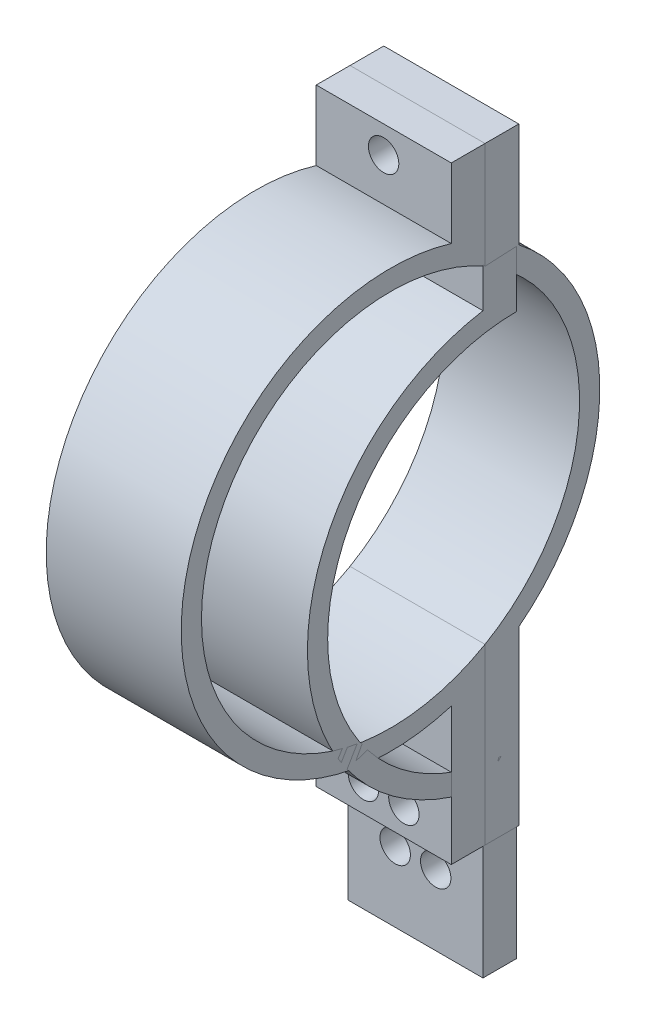
SolidWorks part; units mm, degrees
other "v1"
other "v2.1"
other "v2.2"
ref_plane "Front Plane" through (0, 0, 0) normal (1, 0, 0) x (0, 1, 0)
ref_plane "Top Plane" through (0, 0, 0) normal (0, 0, 1) x (0, 1, 0)
ref_plane "Right Plane" through (0, 0, 0) normal (0, 1, 0) x (-1, 0, 0)
sketch "Sketch1" plane through (0, 0, 0) normal (1, 0, 0) x (0, 1, 0)
  line L0 (0, 0) -> (-45, 0)
  line L1 (-45, -5) -> (45, -5)
  line L2 (-45, -5) -> (-45, 5)
  line L3 (-45, 5) -> (45, 5)
  line L4 (45, -5) -> (45, 5)
  line L5 (-45, -5) -> (45, 5) construction
  line L6 (-45, 5) -> (45, -5) construction
  line L7 (-45, 0) -> (0, 0)
  line L8 (0, 0) -> (45, 0)
  circle A0 centre (0, 0) radius 28
  circle A1 centre (0, 0) radius 31
  dimension "D1" = 56
  dimension "D2" = 62
  dimension "D3" = 10
  dimension "D4" = 90
extrude "Boss-Extrude1" add sketch "Sketch1" along normal blind 20 contours L3 A1 A0 | L3 A1 L7 A0 | A1 L3 L2 L0 | A1 L8 L4 L3 | L8 A1 L3 A0 region at (0, -29.3572, 2.5061) region at (0, 29.3572, 2.5061) region at (0, -37.932, 2.5119) region at (0, -29.072, 5.6648) region at (0, 37.932, 2.5119)
sketch "Sketch3" plane through (0, -45, 0) normal (0, -1, 0) x (1, 0, 0)
  line L4 (0, 5) -> (0, 0)
  line L5 (0, 0) -> (20, 0)
  line L6 (20, 0) -> (20, 5)
  line L7 (20, 5) -> (0, 5)
  line L8 (0, 5) -> (0, 0)
  line L9 (0, 0) -> (20, 0)
  line L10 (20, 0) -> (20, 5)
  line L11 (20, 5) -> (0, 5)
  dimension "D1" = 0
extrude "Boss-Extrude2" add sketch "Sketch3" along normal blind 10
sketch "Sketch2" plane through (0, 0, 5) normal (0, 0, 1) x (1, 0, 0)
  line L1 (0, -55) -> (0, -30.5941) construction
  line L3 (0, 30.5941) -> (0, 45) construction
  line L4 (20, -30.5941) -> (0, -30.5941) construction
  circle A2 centre (7, -44.5941) radius 2.25
  circle A3 centre (10, 37.9474) radius 2.25
  circle A4 centre (13, -44.5941) radius 2.25
  dimension "D1" = 4.5
  dimension "D2" = 7
  dimension "D3" = 4.5
  dimension "D4" = 4.5
  dimension "D5" = 6
  dimension "D6" = 10
  dimension "D7" = 14
extrude "Cut-Extrude1" cut sketch "Sketch2" against normal blind 10
sketch "Sketch4" plane through (0, 0, 0) normal (1, 0, 0) x (0, 1, 0)
  line L5 (51.8959, 4.6918) -> (-38.1041, 4.6918)
  line L6 (-38.1041, 9.6918) -> (51.8959, 9.6918)
  line L8 (-38.1041, 9.6918) -> (-38.1041, -0.3082)
  line L9 (-38.1041, -0.3082) -> (51.8959, -0.3082)
  line L10 (51.8959, 9.6918) -> (51.8959, -0.3082)
  circle A0 centre (11.8959, 18.6918) radius 28
  circle A1 centre (11.8959, 18.6918) radius 31
  dimension "D3" = 56
  dimension "D1" = 14
  dimension "D2" = 10
  dimension "D4" = 90
  dimension "D5" = 40
extrude "Boss-Extrude3" add sketch "Sketch4" along normal blind 20 separate body contours A1 L6 L8 L5 | L6 A1 L5 A0 | L6 A1 A0 | L5 A1 L6 A0 | A1 L5 L10 L6 region at (0, 46.254, 7.1177) region at (0, 38.9949, 7.159) region at (0, 39.9854, 10.4296) region at (0, -15.203, 7.159) region at (0, -27.4691, 7.1526)
sketch "Sketch5" plane through (0, 0, 9.6918) normal (0, 0, 1) x (1, 0, 0)
  line L0 (20, 51.8959) -> (0, 51.8959) construction
  line L1 (20, -38.1041) -> (0, -38.1041) construction
  circle A0 centre (6.9794, -34.0267) radius 2.25
  circle A1 centre (9.9794, 47.8959) radius 2.25
  circle A2 centre (12.9794, -34.1041) radius 2.25
  dimension "D1" = 4
  dimension "D2" = 4
extrude "Boss-Extrude4" add sketch "Sketch4<3>" along normal blind 20 separate body contours A1 L9 L10 L5 | L9 A1 L5 A0 | L9 A1 A0 | L5 A1 L9 A0 | A1 L5 L8 L9 region at (0, 44.96, 2.0966) region at (0, 36.2254, 2.1332) region at (0, 11.8959, -11.8038) region at (0, -12.4335, 2.1332) region at (0, -26.1808, 2.1366)
sketch "Sketch4<3>" plane through (0, 0, 0) normal (1, 0, 0) x (0, 1, 0) same geometry as "Sketch4"
extrude "Cut-Extrude2" cut sketch "Sketch5" against normal blind 20
